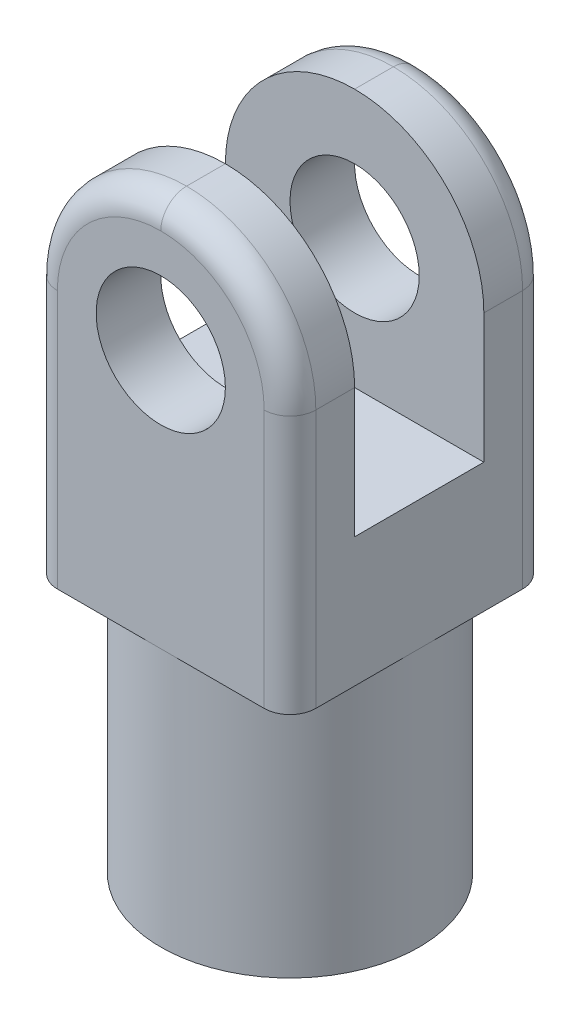
SolidWorks part; units mm, degrees
ref_plane "Front Plane" through (0, 0, 0) normal (0, 0, 1) x (1, 0, 0)
ref_plane "Top Plane" through (0, 0, 0) normal (0, 1, 0) x (1, 0, 0)
ref_plane "Right Plane" through (0, 0, 0) normal (1, 0, 0) x (0, 0, -1)
sketch "Sketch1" plane through (0, 0, 0) normal (0, 1, 0) x (1, 0, 0)
  line L1 (-50, 50) -> (50, 50)
  line L2 (-50, 50) -> (-50, -50)
  line L3 (-50, -50) -> (50, -50)
  line L4 (50, 50) -> (50, -50)
  line L5 (-50, 50) -> (50, -50) construction
  line L6 (-50, -50) -> (50, 50) construction
  point P0 (0, 0)
  dimension "D1" = 100
  dimension "D2" = 100
extrude "Boss-Extrude1" add sketch "Sketch1" along normal blind 150
sketch "Sketch2" plane through (0, 0, 0) normal (0, -1, 0) x (1, 0, 0)
  circle A0 centre (0, 0) radius 50
  circle A1 centre (0, 0) radius 25
extrude "Boss-Extrude2" add sketch "Sketch2" along normal blind 100
sketch "Sketch3" plane through (0, 150, 0) normal (0, 1, 0) x (1, 0, 0)
  line L0 (-50, 50) -> (-50, -50) construction
  line L1 (-50, 25) -> (50, 25)
  line L2 (-50, 25) -> (-50, -25)
  line L3 (-50, -25) -> (50, -25)
  line L4 (50, 25) -> (50, -25)
  line L5 (50, -50) -> (50, 50) construction
  line L6 (50, 50) -> (-50, 50) construction
  line L7 (-50, -50) -> (50, -50) construction
  dimension "D1" = 50
  dimension "D2" = 25
  dimension "D3" = 25
extrude "Cut-Extrude1" cut sketch "Sketch3" against normal blind 100
sketch "Sketch4" plane through (0, 0, 50) normal (0, 0, 1) x (1, 0, 0)
  line L0 (-50, 150) -> (50, 150) construction
  circle A0 centre (0, 100) radius 25
  dimension "D1" = 50
extrude "Cut-Extrude2" cut sketch "Sketch4" against normal through all
fillet "Fillet1" radius 50 4 edges at (50, 150, 37.5) (50, 150, -37.5) (-50, 150, -37.5) (-50, 150, 37.5)
fillet "Fillet2" radius 10 8 edges at (-50, 50, -50) (-35.3553, 135.3553, -50) (35.3553, 135.3553, -50) (-50, 50, 50) (-35.3553, 135.3553, 50) (35.3553, 135.3553, 50) (50, 50, -50) (50, 50, 50)
ref_axis "Axis1" through (0, -100, 0) along (0, 1, 0)
ref_point "Point1"
ref_plane "Plane1" through (0, 0, 0) normal (0, 0, 1) x (1, 0, 0)
ref_axis "Axis2" through (0, 100, 25) along (0, 0, 1)
ref_point "Point2"
